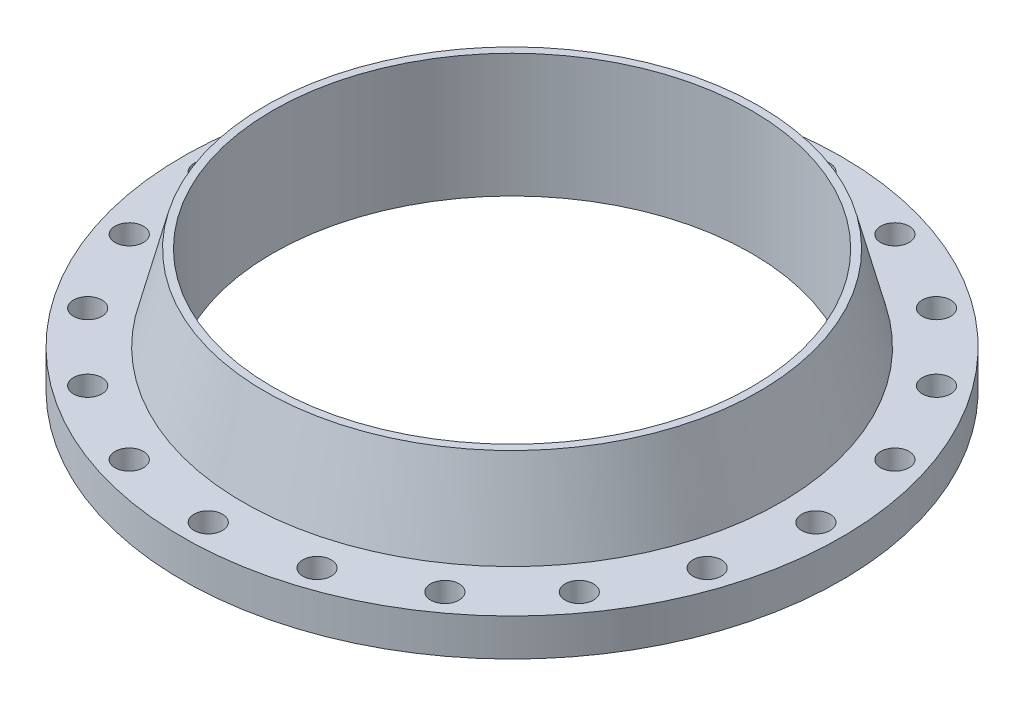
SolidWorks part; units mm, degrees
ref_plane "Front Plane" through (0, 0, 0) normal (0, 0, 1) x (1, 0, 0)
ref_plane "Top Plane" through (0, 0, 0) normal (0, 1, 0) x (1, 0, 0)
ref_plane "Right Plane" through (0, 0, 0) normal (1, 0, 0) x (0, 0, -1)
sketch "Sketch8" plane through (0, 0, 0) normal (0, 0, 1) x (1, 0, 0)
  line L0 (0, 0) -> (0, -0.0625) construction
  line L1 (-11.625, 0) -> (-11.625, 5.94)
  line L2 (-11.625, 0) -> (-11.625, -0.0625)
  line L3 (0, 0) -> (0, 10.2517) construction
  line L4 (-11.625, -0.0625) -> (-13.625, -0.0625)
  line L5 (-13.625, -0.0625) -> (-13.625, 0)
  line L8 (-13.625, 0) -> (-16, 0)
  line L9 (-16, 0) -> (-16, 1.81)
  line L10 (-16, 1.81) -> (-13.06, 1.81)
  line L12 (-12, 5.94) -> (-11.625, 5.94)
  line L14 (-12, 5.94) -> (-13.06, 1.81)
  dimension "D1" = 11.625
  dimension "D2" = 12
  dimension "D3" = 13.06
  dimension "D4" = 13.625
  dimension "D5" = 16
  dimension "D6" = 1.81
  dimension "D7" = 5.94
  dimension "D8" = 0.0625
revolve "Revolve1" add sketch "Sketch8" angle 360 about L3
sketch "Sketch10" plane through (0, 0, 0) normal (0, 1, 0) x (1, 0, 0)
  circle A0 centre (0, 14.75) radius 0.69
  dimension "D1" = 1.38
  dimension "D2" = 14.75
extrude "Cut-Extrude1" cut sketch "Sketch10" along normal blind 6.81
pattern_circular "CirPattern1" count 20 over 360 about axis through (0, 0, 0) along (0, 1, 0) of "Cut-Extrude1" reverse direction yes
